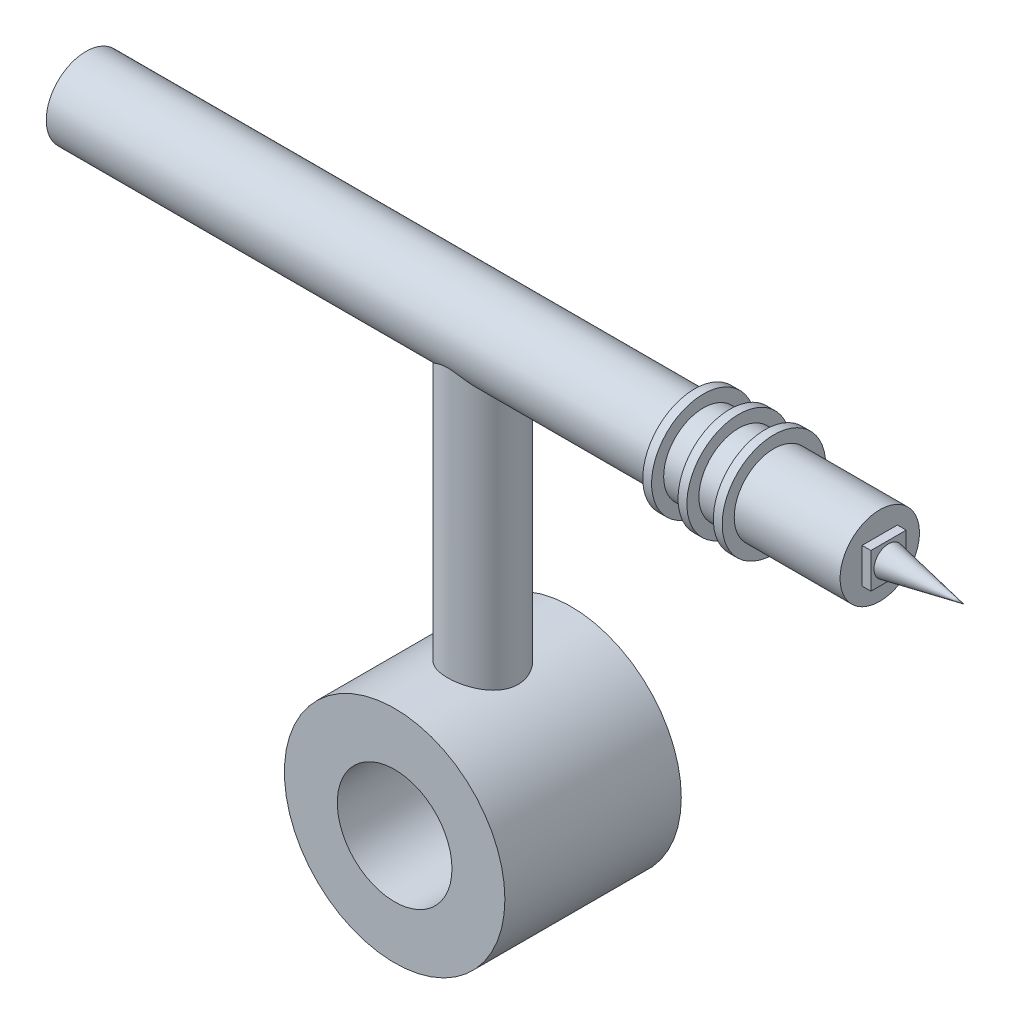
SolidWorks part; units mm, degrees
material "Pure Gold"
ref_plane "Front Plane" through (0, 0, 0) normal (0, 0, 1) x (1, 0, 0)
ref_plane "Top Plane" through (0, 0, 0) normal (0, 1, 0) x (1, 0, 0)
ref_plane "Right Plane" through (0, 0, 0) normal (1, 0, 0) x (0, 0, -1)
other "Configuration Table"
sketch "Sketch2" plane through (0, 0, 0) normal (0, 0, 1) x (1, 0, 0)
  circle A0 centre (0, 0) radius 6.25
  dimension "D1" = 12.5
extrude "Extrude1" add sketch "Sketch2" along normal mid plane 10
sketch "Sketch3" plane through (0, 0, 0) normal (0, 1, 0) x (-1, 0, 0)
  circle A0 centre (0, 0) radius 2
  dimension "D1" = 4
extrude "Extrude2" add sketch "Sketch3" along normal blind 22.5
sketch "Sketch4" plane through (0, 0, 0) normal (1, 0, 0) x (0, 0, -1)
  line L0 (2, 22.5) -> (-2, 22.5) construction
  circle A0 centre (0, 22.5) radius 2.25
  dimension "D1" = 4.5
extrude "Extrude3" add sketch "Sketch4" along normal blind 22.5 and the other way blind 22.5
ref_plane "Plane3" through (12, 0, 0) normal (1, 0, 0) x (0, 0, -1)
sketch "Sketch5" plane through (12, 0, 0) normal (1, 0, 0) x (0, 0, -1)
  circle A0 centre (0, 22.5) radius 2.9338
extrude "Extrude4" add sketch "Sketch5" along normal blind 0.5
sketch "Sketch8" plane through (0, 0, 0) normal (0, 1, 0) x (-1, 0, 0)
  line L0 (-124.0656, -12.0237) -> (-134.7052, -12.0237)
pattern_linear "LPattern1" count 3 spacing 2 along (1, 0, 0) of "Extrude4"
sketch "Sketch9" plane through (22.5, 0, 0) normal (1, 0, 0) x (0, 0, -1)
  line L0 (-1, 21.5) -> (1, 23.5) construction
  line L1 (-1, 23.5) -> (1, 23.5)
  line L2 (-1, 23.5) -> (-1, 21.5)
  line L3 (-1, 21.5) -> (1, 21.5)
  line L4 (1, 23.5) -> (1, 21.5)
  circle A1 centre (0, 22.5) radius 2.25 construction
  point P6 (0, 22.5)
  dimension "D1" = 2
  dimension "D2" = 2
extrude "Extrude6" add sketch "Sketch9" along normal blind 0.5
sketch "Sketch6" plane through (22.5, 0, 0) normal (1, 0, 0) x (0, 0, -1)
  circle A0 centre (0, 22.5) radius 0.925
  dimension "D1" = 1.85
extrude "Extrude5" add sketch "Sketch6" along normal blind 5 draft 11
sketch "Sketch7" plane through (0, 0, 5) normal (0, 0, 1) x (1, 0, 0)
  circle A0 centre (0, 0) radius 3.25
  dimension "D1" = 6.5
extrude "Cut-Extrude1" cut sketch "Sketch7" against normal through all
